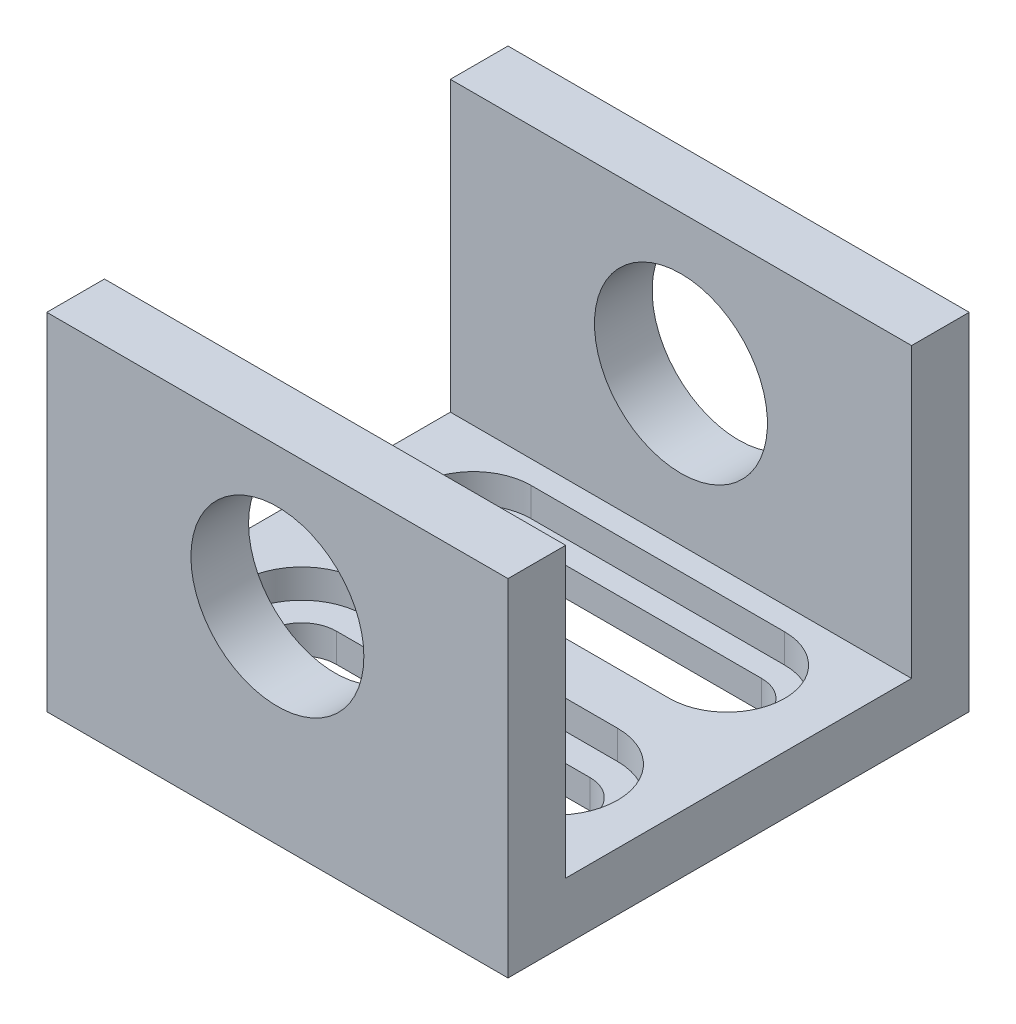
SolidWorks part; units mm, degrees
ref_plane "Front Plane" through (0, 0, 0) normal (0, 0, 1) x (1, 0, 0)
ref_plane "Top Plane" through (0, 0, 0) normal (0, 1, 0) x (1, 0, 0)
ref_plane "Right Plane" through (0, 0, 0) normal (1, 0, 0) x (0, 0, -1)
sketch "Sketch1" plane through (-35.1459, 0, 0) normal (1, 0, 0) x (0, 0, -1)
  line L1 (0, 0) -> (-19.05, 0)
  line L3 (0, 3.175) -> (-19.05, 3.175)
  line L5 (3.175, 19.05) -> (0, 19.05)
  line L6 (3.175, 19.05) -> (3.175, 0)
  line L7 (3.175, 0) -> (0, 0)
  line L8 (0, 19.05) -> (0, 3.175)
  line L13 (-19.05, 0) -> (-22.225, 0)
  line L14 (-19.05, 3.175) -> (-19.05, 19.05)
  line L15 (-19.05, 19.05) -> (-22.225, 19.05)
  line L16 (-22.225, 0) -> (-22.225, 19.05)
  dimension "D2" = 3.175
  dimension "D3" = 3.175
  dimension "D4" = 19.05
  dimension "D5" = 19.05
extrude "Boss-Extrude2" add sketch "Sketch1" along normal blind 25.4
sketch "Sketch3" plane through (0, 0, -3.175) normal (0, 0, -1) x (-1, 0, 0)
  line L0 (9.7459, 0) -> (35.1459, 0) construction
  line L2 (35.1459, 0) -> (35.1459, 19.05) construction
  circle A0 centre (22.4459, 11.3665) radius 4.7625
  dimension "D1" = 11.3665
  dimension "D2" = 12.7
extrude "Cut-Extrude1" cut sketch "Sketch3" against normal blind 36.576
sketch "Sketch4" plane through (0, 3.175, 0) normal (0, 1, 0) x (1, 0, 0)
  line L1 (-29.4309, -1.27) -> (-15.4609, -1.27)
  line L3 (-29.4309, -2.54) -> (-15.4609, -2.54)
  line L5 (-29.4309, -6.35) -> (-15.4609, -6.35)
  line L7 (-29.4309, -7.62) -> (-15.4609, -7.62)
  line L9 (-9.7459, -19.05) -> (-35.1459, -19.05) construction
  line L10 (-29.4309, -1.27) -> (-15.4609, -1.27)
  line L11 (-15.4609, -7.62) -> (-29.4309, -7.62)
  arc A0 (-29.4309, -2.54) -> (-29.4309, -6.35) centre (-29.4309, -4.445) ccw
  arc A1 (-29.4309, -1.27) -> (-29.4309, -7.62) centre (-29.4309, -4.445) ccw
  arc A2 (-15.4609, -2.54) -> (-15.4609, -6.35) centre (-15.4609, -4.445) cw
  arc A3 (-15.4609, -1.27) -> (-15.4609, -7.62) centre (-15.4609, -4.445) cw
  arc A4 (-29.4309, -1.27) -> (-29.4309, -7.62) centre (-29.4309, -4.445) ccw
  arc A5 (-15.4609, -1.27) -> (-15.4609, -7.62) centre (-15.4609, -4.445) cw
  dimension "D1" = 1.27
  dimension "D4" = 1.27
  dimension "D5" = 3.81
  dimension "D6" = 12.7
extrude "Cut-Extrude2" cut sketch "Sketch4" against normal blind 66.04 contours L3 A2 L5 A0
sketch "Sketch7" plane through (0, 3.175, 0) normal (0, 1, 0) x (1, 0, 0)
  line L1 (-29.4309, -2.54) -> (-15.4609, -2.54)
  line L3 (-29.4309, -1.27) -> (-15.4609, -1.27)
  line L5 (-29.4309, -6.35) -> (-15.4609, -6.35)
  line L7 (-29.4309, -7.62) -> (-15.4609, -7.62)
  arc A0 (-29.4309, -1.27) -> (-29.4309, -7.62) centre (-29.4309, -4.445) ccw
  arc A1 (-15.4609, -1.27) -> (-15.4609, -7.62) centre (-15.4609, -4.445) cw
  dimension "D1" = 1.27
  dimension "D2" = 13.97
  dimension "D3" = 1.27
  dimension "D4" = 13.97
extrude "Cut-Extrude3" cut sketch "Sketch7" against normal blind 1.5875 contours L3 A1 L7 A0
sketch "Sketch8" plane through (0, 3.175, 0) normal (0, 1, 0) x (1, 0, 0)
  line L1 (-29.4309, -11.9938) -> (-15.4609, -11.9938)
  line L3 (-29.4309, -15.8038) -> (-15.4609, -15.8038)
  line L5 (-29.4309, -10.4698) -> (-15.4609, -10.4698)
  line L6 (-15.4609, -17.3278) -> (-29.4309, -17.3278)
  arc A0 (-15.4609, -15.8038) -> (-15.4609, -11.9938) centre (-15.4609, -13.8988) ccw
  arc A1 (-29.4309, -11.9938) -> (-29.4309, -15.8038) centre (-29.4309, -13.8988) ccw
  arc A3 (-29.4309, -10.4698) -> (-29.4309, -17.3278) centre (-29.4309, -13.8988) ccw
  arc A5 (-15.4609, -17.3278) -> (-15.4609, -10.4698) centre (-15.4609, -13.8988) ccw
  dimension "D1" = 3.81
extrude "Cut-Extrude4" cut sketch "Sketch8" against normal blind 1.5875 contours L1 A1 L3 A0 | L6 A5 L5 A3 A1 L1 A0 L3 region at (-22.4459, 3.175, 13.8988) region at (-22.4459, 3.175, 10.6891)
extrude "Cut-Extrude5" cut sketch "Sketch8<3>" against normal through all contours L1 A1 L3 A0 region at (-22.4459, 3.175, 13.8988)
sketch "Sketch8<3>" plane through (0, 3.175, 0) normal (0, 1, 0) x (1, 0, 0) same geometry as "Sketch8"
